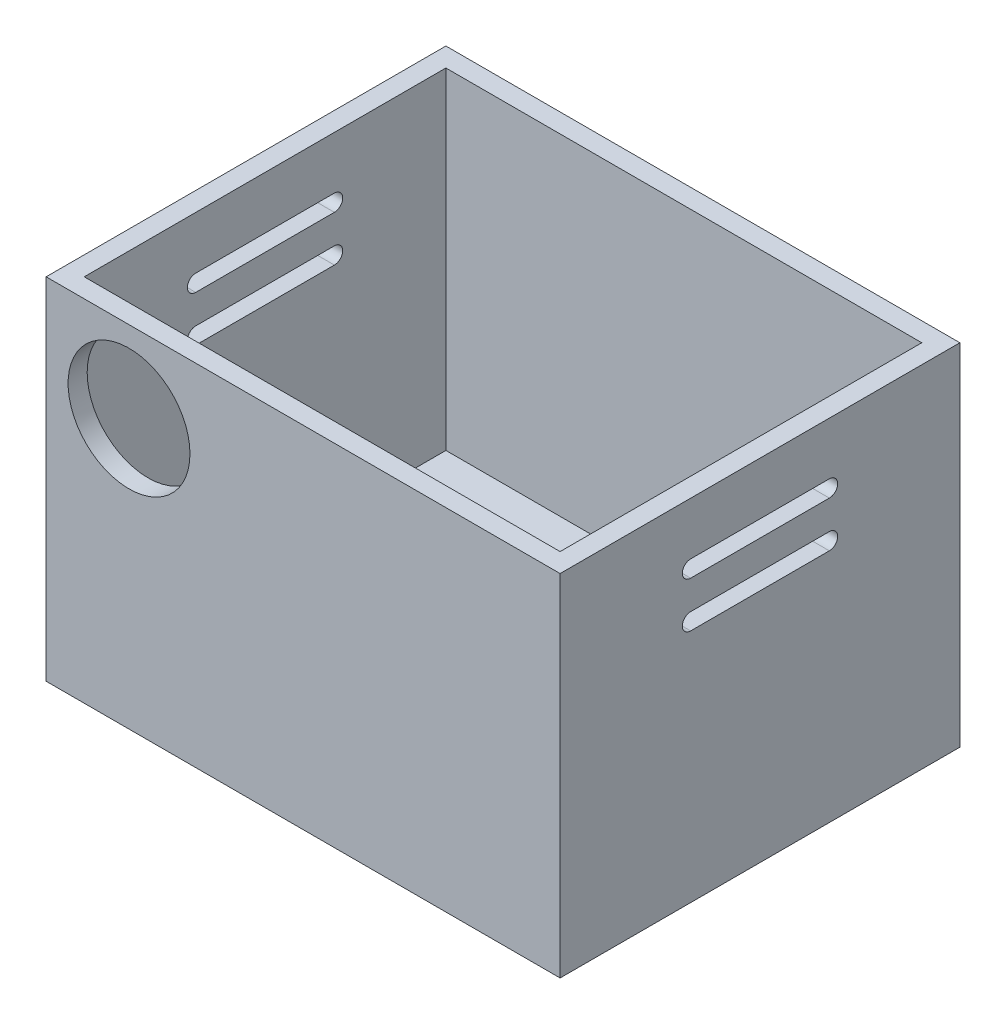
SolidWorks part; units mm, degrees
ref_plane "Front Plane" through (0, 0, 0) normal (0, 0, 1) x (1, 0, 0)
ref_plane "Top Plane" through (0, 0, 0) normal (0, 1, 0) x (1, 0, 0)
ref_plane "Right Plane" through (0, 0, 0) normal (1, 0, 0) x (0, 0, -1)
sketch "Sketch1" plane through (0, 0, 0) normal (0, 1, 0) x (1, 0, 0)
  line L1 (-42.8625, 33.3375) -> (42.8625, 33.3375)
  line L2 (-42.8625, 33.3375) -> (-42.8625, -33.3375)
  line L3 (-42.8625, -33.3375) -> (42.8625, -33.3375)
  line L4 (42.8625, 33.3375) -> (42.8625, -33.3375)
  line L5 (-42.8625, 33.3375) -> (42.8625, -33.3375) construction
  line L6 (-42.8625, -33.3375) -> (42.8625, 33.3375) construction
  line L8 (-42.8625, 16.04) -> (-42.8625, -5.457)
  point P0 (0, 0)
  dimension "D1" = 85.725
  dimension "D2" = 66.675
extrude "Boss-Extrude2" add sketch "Sketch1" along normal blind 58.42 contours L1 L4 L3 L2
shell "Shell1" thickness 3.175 removed face at (0, 58.42, 0)
hole_wizard "Hole1" positions "Sketch12" profile "Sketch14" legacy end condition up to next
sketch "Sketch12" plane through (0, 0, 33.3375) normal (0, 0, 1) x (1, 0, 0)
  point P10 (-29.0335, 44.8588)
  point P40 (-29.0335, 44.8588)
sketch "Sketch14" plane through (-29.0335, 44.8588, 33.3375) normal (1, 0, 0) x (0, -1, 0)
  line L0 (0, 0) -> (0, 66.675)
  line L1 (0, 66.675) -> (10.16, 66.675)
  line L2 (10.16, 66.675) -> (10.16, 0)
  line L3 (10.16, 0) -> (0, 0)
  line L4 (0, 110) -> (0, -10) construction
  dimension "Diameter" = 20.32
  dimension "Depth" = 66.675
hole_wizard "7/64 (0.10938) Diameter Slot1" positions "Sketch17" profile "Sketch19" size "7/64" standard "ANSI Inch" slot yes end condition through all
sketch "Sketch17" plane through (42.8625, 0, 0) normal (1, 0, 0) x (0, 0, -1)
  line L0 (12.954, 40.64) -> (-12.954, 40.64) construction
  point P0 (0, 40.64)
  dimension "D1" = 25.908
sketch "Sketch19" plane through (42.8625, 40.64, 0) normal (0, 1, 0) x (0, 0, -1)
  line L0 (0, 0) -> (0, 85.725)
  line L1 (0, 85.725) -> (1.3891, 85.725)
  line L2 (1.3891, 85.725) -> (1.3891, 0)
  line L5 (1.3891, 0) -> (0, 0)
  line L11 (0, -6.35) -> (0, 107.95) construction
  dimension "Thru Hole Dia." = 2.7783
  dimension "Thru Hole Depth" = 85.725
hole_wizard "7/64 (0.10938) Diameter Slot2" positions "Sketch20" profile "Sketch21" size "7/64" standard "ANSI Inch" slot yes end condition through all
sketch "Sketch20" plane through (42.8625, 0, 0) normal (1, 0, 0) x (0, 0, -1)
  line L0 (12.954, 48.26) -> (-12.954, 48.26) construction
  point P0 (0, 48.26)
  dimension "D1" = 25.908
sketch "Sketch21" plane through (42.8625, 48.26, 0) normal (0, 1, 0) x (0, 0, -1)
  line L0 (0, 0) -> (0, 85.725)
  line L1 (0, 85.725) -> (1.3891, 85.725)
  line L2 (1.3891, 85.725) -> (1.3891, 0)
  line L5 (1.3891, 0) -> (0, 0)
  line L11 (0, -6.35) -> (0, 107.95) construction
  dimension "Thru Hole Dia." = 2.7783
  dimension "Thru Hole Depth" = 85.725
equation "\"3.00mmin\"=3"
equation "\"3.00inn\"=3"
equation "\"0.50inn\"=0.1"
